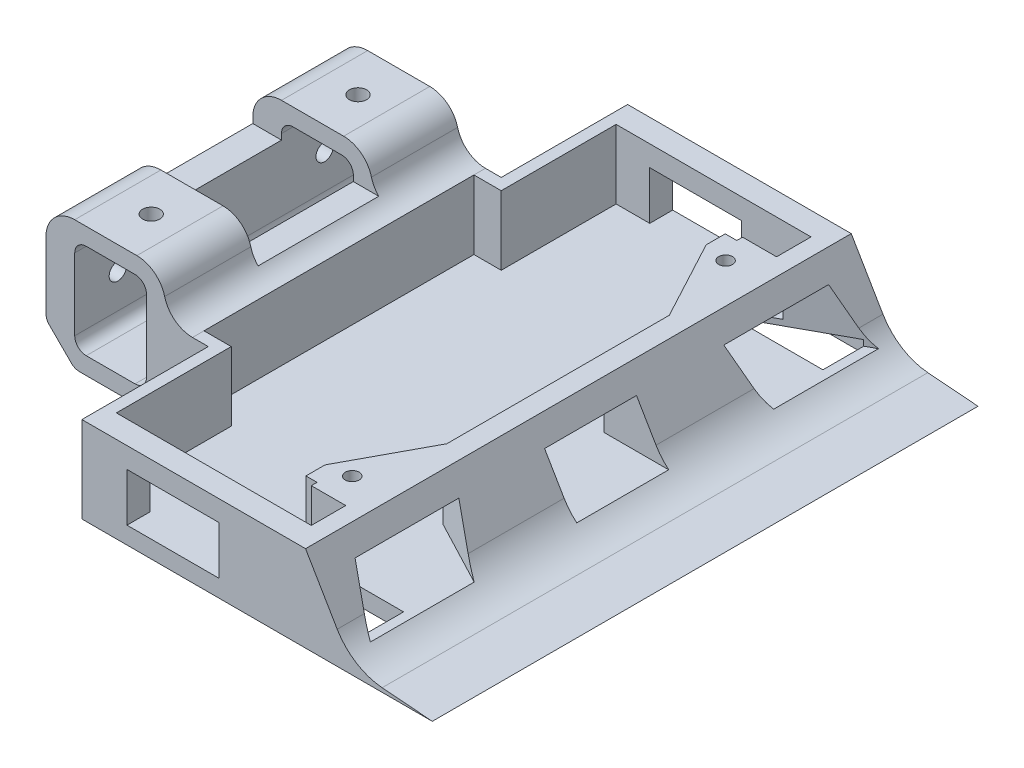
SolidWorks part; units mm, degrees
ref_plane "Front Plane" through (0, 0, 0) normal (0, 0, 1) x (1, 0, 0)
ref_plane "Top Plane" through (0, 0, 0) normal (0, 1, 0) x (1, 0, 0)
ref_plane "Right Plane" through (0, 0, 0) normal (1, 0, 0) x (0, 0, -1)
sketch "Sketch1" plane through (0, 0, 0) normal (0, 1, 0) x (1, 0, 0)
  line L1 (-49.665, 50.1777) -> (45.335, 50.1777)
  line L2 (-49.665, 50.1777) -> (-49.665, -44.8223)
  line L3 (-49.665, -44.8223) -> (45.335, -44.8223)
  line L4 (45.335, 50.1777) -> (45.335, -44.8223)
  dimension "D1" = 95
  dimension "D2" = 95
extrude "Boss-Extrude1" add sketch "Sketch1" along normal blind 20
sketch "Sketch2" plane through (45.335, 0, 0) normal (1, 0, 0) x (0, 0, -1)
  line L0 (-44.8223, 20) -> (-44.8223, 0) construction
  line L1 (-4.8223, 3) -> (10.1777, 3)
  line L2 (-4.8223, 3) -> (-4.8223, 11.4)
  line L3 (-4.8223, 11.4) -> (10.1777, 11.4)
  line L4 (10.1777, 3) -> (10.1777, 11.4)
  line L5 (50.1777, 20) -> (50.1777, 0) construction
  line L6 (-44.8223, 0) -> (50.1777, 0) construction
  dimension "D1" = 15
  dimension "D2" = 8.4
  dimension "D3" = 40
  dimension "D4" = 40
  dimension "D5" = 3
extrude "Cut-Extrude1" cut sketch "Sketch2" against normal blind 50
sketch "Sketch6" plane through (0, 0, 44.8223) normal (0, 0, 1) x (1, 0, 0)
  line L0 (45.335, 0) -> (31.4163, 1.1197)
  line L1 (31.4163, 1.1197) -> (20.335, 20)
  line L2 (-49.665, 20) -> (45.335, 20) construction
  line L3 (20.335, 20) -> (45.335, 20)
  line L4 (45.335, 20) -> (45.335, 0)
  dimension "D1" = 25
extrude "Cut-Extrude3" cut sketch "Sketch6" against normal blind 100
fillet "Fillet1" radius 10 1 edges at (31.4163, 1.1197, -2.6777)
sketch "Sketch7" plane through (0, 20, 0) normal (0, 1, 0) x (1, 0, 0)
  line L0 (11.3607, -29.8223) -> (18.335, -16.5423)
  line L1 (18.335, -16.5423) -> (9.4816, -11.8928)
  line L2 (9.4816, -11.8928) -> (2.5073, -25.1728)
  line L3 (2.5073, -25.1728) -> (11.3607, -29.8223)
  line L4 (20.335, 50.1777) -> (20.335, -44.8223) construction
  line L5 (-49.665, -44.8223) -> (20.335, -44.8223) construction
  line L6 (18.335, 22.0203) -> (11.132, 35.1777)
  line L7 (11.132, 35.1777) -> (2.3604, 30.3757)
  line L8 (2.3604, 30.3757) -> (9.5634, 17.2183)
  line L9 (9.5634, 17.2183) -> (18.335, 22.0203)
  line L10 (20.335, 50.1777) -> (-49.665, 50.1777) construction
  dimension "D1" = 10
  dimension "D2" = 15
  dimension "D3" = 2
  dimension "D4" = 15
  dimension "D5" = 10
  dimension "D6" = 15
  dimension "D7" = 15
  dimension "D8" = 2
extrude "Cut-Extrude4" cut sketch "Sketch7" against normal blind 17
sketch "Sketch8" plane through (12.3274, 0, 6.474) normal (0.8853, 0, 0.465) x (0.465, 0, -0.8853)
  line L0 (-21.1206, 3) -> (-21.1206, 20) construction
  line L1 (-21.1206, 3) -> (-6.1206, 3)
  line L2 (-21.1206, 3) -> (-21.1206, 11.4)
  line L3 (-21.1206, 11.4) -> (-6.1206, 11.4)
  line L4 (-6.1206, 3) -> (-6.1206, 11.4)
  line L5 (-6.1206, 3) -> (-21.1206, 3) construction
  line L6 (-6.1206, 3) -> (-6.1206, 20) construction
  dimension "D1" = 8.4
extrude "Cut-Extrude5" cut sketch "Sketch8" against normal blind 4
sketch "Sketch9" plane through (14.6107, 0, -7.9986) normal (0.8772, 0, -0.4802) x (-0.4802, 0, -0.8772)
  line L0 (25.5109, 3) -> (10.5109, 3) construction
  line L1 (25.5109, 3) -> (10.5109, 3)
  line L2 (25.5109, 3) -> (25.5109, 11.4)
  line L3 (25.5109, 11.4) -> (10.5109, 11.4)
  line L4 (10.5109, 3) -> (10.5109, 11.4)
  line L5 (25.5109, 3) -> (25.5109, 20) construction
  line L6 (10.5109, 3) -> (10.5109, 20) construction
  dimension "D1" = 8.4
extrude "Cut-Extrude6" cut sketch "Sketch9" against normal blind 4
sketch "Sketch10" plane through (8.7861, 0, 4.6142) normal (0.8853, 0, 0.465) x (0.465, 0, -0.8853)
  line L0 (-21.1206, 11.4) -> (-21.1206, 3) construction
  line L1 (-21.1206, 3) -> (-6.1206, 3)
  line L2 (-21.1206, 3) -> (-21.1206, 11.4)
  line L3 (-21.1206, 11.4) -> (-6.1206, 11.4)
  line L4 (-6.1206, 3) -> (-6.1206, 11.4)
  line L5 (-21.1206, 3) -> (-6.1206, 3) construction
  line L6 (-6.1206, 3) -> (-6.1206, 11.4) construction
extrude "Cut-Extrude7" cut sketch "Sketch10" along normal blind 100
sketch "Sketch11" plane through (11.102, 0, -6.0778) normal (0.8772, 0, -0.4802) x (-0.4802, 0, -0.8772)
  line L0 (10.5109, 3) -> (25.5109, 3) construction
  line L1 (25.5109, 3) -> (10.5109, 3)
  line L2 (25.5109, 3) -> (25.5109, 11.4)
  line L3 (25.5109, 11.4) -> (10.5109, 11.4)
  line L4 (10.5109, 3) -> (10.5109, 11.4)
  line L5 (25.5109, 3) -> (25.5109, 11.4) construction
  line L6 (10.5109, 11.4) -> (10.5109, 3) construction
extrude "Cut-Extrude8" cut sketch "Sketch11" along normal blind 100
sketch "Sketch12" plane through (0, 0, 44.8223) normal (0, 0, 1) x (1, 0, 0)
  line L1 (-49.665, 20) -> (46.5626, 20)
  line L2 (-49.665, 20) -> (-49.665, 15)
  line L3 (-49.665, 15) -> (46.5626, 15)
  line L4 (46.5626, 20) -> (46.5626, 15)
  dimension "D1" = 5
extrude "Cut-Extrude9" cut sketch "Sketch12" against normal blind 100
sketch "Sketch14" plane through (11.102, 0, -6.0778) normal (0.8772, 0, -0.4802) x (-0.4802, 0, -0.8772)
  line L0 (10.5109, 11.4) -> (10.5109, 3) construction
  line L1 (10.5109, 3) -> (26.5109, 3)
  line L2 (10.5109, 3) -> (10.5109, 11.4)
  line L3 (10.5109, 11.4) -> (26.5109, 11.4)
  line L4 (26.5109, 3) -> (26.5109, 11.4)
  line L5 (10.5109, 3) -> (25.5109, 3) construction
  line L6 (25.5109, 11.4) -> (10.5109, 11.4) construction
  dimension "D1" = 16
extrude "Cut-Extrude10" cut sketch "Sketch14" along normal blind 100
sketch "Sketch15" plane through (8.7861, 0, 4.6142) normal (0.8853, 0, 0.465) x (0.465, 0, -0.8853)
  line L0 (-6.1206, 3) -> (-6.1206, 11.4) construction
  line L1 (-6.1206, 3) -> (-22.1206, 3)
  line L2 (-6.1206, 3) -> (-6.1206, 11.4)
  line L3 (-6.1206, 11.4) -> (-22.1206, 11.4)
  line L4 (-22.1206, 3) -> (-22.1206, 11.4)
  dimension "D1" = 8.4
  dimension "D2" = 16
extrude "Cut-Extrude11" cut sketch "Sketch15" along normal blind 100
sketch "Sketch16" plane through (-4.665, 0, 0) normal (1, 0, 0) x (0, 0, -1)
  line L0 (-4.8223, 3) -> (-4.8223, 5.6084) construction
  line L1 (-5.3223, 3) -> (10.6777, 3)
  line L2 (-5.3223, 3) -> (-5.3223, 11.4)
  line L3 (-5.3223, 11.4) -> (10.6777, 11.4)
  line L4 (10.6777, 3) -> (10.6777, 11.4)
  line L5 (-5.3223, 3) -> (10.6777, 11.4) construction
  line L6 (-5.3223, 11.4) -> (10.6777, 3) construction
  line L7 (50.1777, 0) -> (-44.8223, 0) construction
  point P0 (2.6777, 7.2)
  point P5 (-4.8223, 4.3042)
  dimension "D1" = 8.4
  dimension "D2" = 16
  dimension "D3" = 0.5
  dimension "D4" = 3
extrude "Cut-Extrude13" cut sketch "Sketch16" along normal blind 100
sketch "Sketch19" plane through (0, 15, 0) normal (0, 1, 0) x (1, 0, 0)
  line L0 (12.1654, -30.8097) -> (19.7472, -16.7201)
  line L1 (12.1851, 36.1278) -> (12.1851, 48.1777)
  line L2 (12.1851, 48.1777) -> (-11.5945, 48.1777)
  line L6 (2.5073, -25.1728) -> (11.3607, -29.8223) construction
  line L7 (12.1851, 36.1278) -> (19.7442, 22.026)
  line L10 (19.7442, 22.026) -> (19.7472, -16.7201)
  line L11 (12.1654, -30.8097) -> (12.1654, -42.8223)
  line L12 (12.1654, -42.8223) -> (-11.5945, -42.8223)
  line L13 (-11.5945, -42.8223) -> (-11.5945, 48.1777)
  line L17 (-49.665, -44.8223) -> (23.2696, -44.8223) construction
  dimension "D4" = 0.5
  dimension "D7" = 2
extrude "Cut-Extrude16" cut sketch "Sketch19" against normal blind 12
sketch "Sketch21" plane through (0, 3, 0) normal (0, 1, 0) x (1, 0, 0)
  line L0 (-11.5945, 48.1777) -> (-11.5945, -42.8223) construction
  line L1 (12.1851, 48.1777) -> (-11.5945, 48.1777)
  line L2 (12.1851, 48.1777) -> (12.1851, 46.1777)
  line L3 (12.1851, 46.1777) -> (-11.5945, 46.1777)
  line L4 (-11.5945, 48.1777) -> (-11.5945, 46.1777)
  dimension "D1" = 2
extrude "Boss-Extrude2" add sketch "Sketch21" along normal blind 12
sketch "Sketch23" plane through (0, 3, 0) normal (0, 1, 0) x (1, 0, 0)
  line L0 (-11.5945, 46.1777) -> (-11.5945, -42.8223) construction
  line L1 (12.1654, -42.8223) -> (-11.5945, -42.8223)
  line L2 (12.1654, -42.8223) -> (12.1654, -40.8223)
  line L3 (12.1654, -40.8223) -> (-11.5945, -40.8223)
  line L4 (-11.5945, -42.8223) -> (-11.5945, -40.8223)
  dimension "D1" = 2
extrude "Boss-Extrude3" add sketch "Sketch23" along normal blind 12
sketch "Sketch24" plane through (0, 0, -46.1777) normal (0, 0, 1) x (1, 0, 0)
  line L0 (-11.5945, 3) -> (12.1851, 3) construction
  line L1 (-7.8145, 3) -> (7.1855, 3)
  line L2 (-7.8145, 3) -> (-7.8145, 11.4)
  line L3 (-7.8145, 11.4) -> (7.1855, 11.4)
  line L4 (7.1855, 3) -> (7.1855, 11.4)
  line L5 (-11.5945, 15) -> (-11.5945, 3) construction
  dimension "D1" = 15
  dimension "D2" = 8.4
  dimension "D3" = 3.78
  dimension "D4" = 4.9995
extrude "Cut-Extrude19" cut sketch "Sketch24" against normal blind 100 and the other way blind 100
sketch "Sketch26" plane through (0, 15, 0) normal (0, 1, 0) x (1, 0, 0)
  line L0 (-49.665, 50.1777) -> (23.2696, 50.1777) construction
  line L1 (-49.665, -44.8223) -> (-29.665, -44.8223)
  line L2 (-49.665, -44.8223) -> (-49.665, 50.1777)
  line L3 (-49.665, 50.1777) -> (-29.665, 50.1777)
  line L4 (-29.665, -44.8223) -> (-29.665, 50.1777)
  dimension "D1" = 20
extrude "Boss-Extrude4" add sketch "Sketch26" along normal blind 20
sketch "Sketch31" plane through (-29.665, 0, 0) normal (1, 0, 0) x (0, 0, -1)
  line L1 (-44.8223, 35) -> (50.1777, 35)
  line L2 (-44.8223, 35) -> (-44.8223, 15)
  line L3 (-44.8223, 15) -> (50.1777, 15)
  line L4 (50.1777, 35) -> (50.1777, 15)
extrude "Boss-Extrude6" add sketch "Sketch31" along normal blind 10
sketch "Sketch32" plane through (0, 0, -50.1777) normal (0, 0, -1) x (-1, 0, 0)
  line L0 (49.665, 35) -> (49.665, 0) construction
  line L1 (38.915, 19.5) -> (26.415, 19.5)
  line L2 (38.915, 19.5) -> (38.915, 3)
  line L3 (38.915, 3) -> (26.415, 3)
  line L4 (26.415, 19.5) -> (26.415, 3)
  line L5 (-45.335, 0) -> (49.665, 0) construction
  dimension "D1" = 12.5
  dimension "D2" = 16.5
  dimension "D3" = 10.75
  dimension "D4" = 3
extrude "Cut-Extrude22" cut sketch "Sketch32" against normal blind 100
sketch "Sketch33" plane through (0, 0, -50.1777) normal (0, 0, -1) x (-1, 0, 0)
  line L0 (19.665, 35) -> (49.665, 35) construction
  line L1 (19.665, 15) -> (23.415, 15)
  line L2 (19.665, 15) -> (19.665, 35)
  line L3 (19.665, 35) -> (23.415, 35)
  line L4 (23.415, 15) -> (23.415, 35)
  line L5 (26.415, 19.5) -> (26.415, 3) construction
  dimension "D1" = 3
extrude "Cut-Extrude23" cut sketch "Sketch33" against normal blind 100
sketch "Sketch34" plane through (0, 0, -50.1777) normal (0, 0, -1) x (-1, 0, 0)
  line L0 (49.665, 35) -> (49.665, 0) construction
  line L1 (23.415, 35) -> (49.665, 35)
  line L2 (23.415, 35) -> (23.415, 22.5)
  line L3 (23.415, 22.5) -> (49.665, 22.5)
  line L4 (49.665, 35) -> (49.665, 22.5)
  dimension "D1" = 3
extrude "Cut-Extrude24" cut sketch "Sketch34" against normal blind 100
sketch "Sketch35" plane through (0, 0, -50.1777) normal (0, 0, -1) x (-1, 0, 0)
  line L1 (49.665, 0) -> (15.665, 0)
  line L2 (49.665, 0) -> (49.665, 47.0729)
  line L3 (49.665, 47.0729) -> (15.665, 47.0729)
  line L4 (15.665, 0) -> (15.665, 47.0729)
  dimension "D1" = 34
extrude "Cut-Extrude25" cut sketch "Sketch35" against normal blind 22
sketch "Sketch36" plane through (0, 0, 44.8223) normal (0, 0, 1) x (1, 0, 0)
  line L1 (-49.665, 0) -> (-15.665, 0)
  line L2 (-49.665, 0) -> (-49.665, 30.6044)
  line L3 (-49.665, 30.6044) -> (-15.665, 30.6044)
  line L4 (-15.665, 0) -> (-15.665, 30.6044)
  dimension "D1" = 34
extrude "Cut-Extrude26" cut sketch "Sketch36" against normal blind 22
sketch "Sketch37" plane through (0, 22.5, 0) normal (0, 1, 0) x (1, 0, 0)
  line L0 (-49.665, -22.8223) -> (-49.665, 28.1777) construction
  line L1 (-49.665, 13.1777) -> (-23.415, 13.1777)
  line L2 (-49.665, 13.1777) -> (-49.665, -7.8223)
  line L3 (-49.665, -7.8223) -> (-23.415, -7.8223)
  line L4 (-23.415, 13.1777) -> (-23.415, -7.8223)
  line L5 (-23.415, 28.1777) -> (-23.415, -22.8223) construction
  dimension "D1" = 15
  dimension "D2" = 15
extrude "Cut-Extrude28" cut sketch "Sketch37" against normal blind 6
sketch "Sketch38" plane through (0, 0, 22.8223) normal (0, 0, 1) x (1, 0, 0)
  line L0 (-49.665, 0) -> (-15.665, 0) construction
  line L1 (-49.665, 22.5) -> (-43.915, 22.5)
  line L2 (-49.665, 22.5) -> (-49.665, 0)
  line L3 (-49.665, 0) -> (-43.915, 0)
  line L4 (-43.915, 22.5) -> (-43.915, 0)
  line L5 (-38.915, 19.5) -> (-38.915, 3) construction
  dimension "D1" = 5
extrude "Cut-Extrude29" cut sketch "Sketch38" against normal blind 100
chamfer "Chamfer1" distance 5 angle 45 1 edges at (-43.915, 0, -2.6777)
sketch "Sketch39" plane through (0, 15, 0) normal (0, 1, 0) x (1, 0, 0)
  line L0 (-15.665, -22.8223) -> (-15.665, -44.8223) construction
  line L1 (-11.5945, 46.1777) -> (-13.665, 46.1777)
  line L2 (-11.5945, 46.1777) -> (-11.5945, -40.8223)
  line L3 (-11.5945, -40.8223) -> (-13.665, -40.8223)
  line L4 (-13.665, 46.1777) -> (-13.665, -40.8223)
  line L5 (-15.665, -44.8223) -> (23.2696, -44.8223) construction
  dimension "D1" = 2
  dimension "D2" = 4
extrude "Cut-Extrude30" cut sketch "Sketch39" against normal blind 12
fillet "Fillet4" radius 5 1 edges at (-23.415, 15, -2.6777)
fillet "Fillet5" radius 5 2 edges at (-23.415, 22.5, 15.3223) (-23.415, 22.5, -20.6777)
sketch "Sketch40" plane through (0, 15, 0) normal (0, 1, 0) x (1, 0, 0)
  line L0 (-13.665, 46.1777) -> (-13.665, -40.8223) construction
  line L1 (-13.665, -20.8223) -> (-18.415, -20.8223)
  line L2 (-13.665, -20.8223) -> (-13.665, 26.1777)
  line L3 (-13.665, 26.1777) -> (-18.415, 26.1777)
  line L4 (-18.415, -20.8223) -> (-18.415, 26.1777)
  line L5 (-18.415, 28.1777) -> (-18.415, -22.8223) construction
  dimension "D1" = 2
  dimension "D2" = 2
extrude "Cut-Extrude31" cut sketch "Sketch40" against normal blind 12
fillet "Fillet6" radius 5 2 edges at (-43.915, 22.5, -20.6777) (-43.915, 22.5, 15.3223)
sketch "Sketch46" plane through (0, 0, 0) normal (0, -1, 0) x (-1, 0, 0)
  line L0 (15.665, -44.8223) -> (-45.335, -44.8223) construction
  line L1 (-29.335, -42.8223) -> (-12.335, -42.8223)
  line L2 (-29.335, -42.8223) -> (-29.335, -33.8223)
  line L3 (-29.335, -33.8223) -> (-12.335, -33.8223)
  line L4 (-12.335, -42.8223) -> (-12.335, -33.8223)
  line L5 (-45.335, -44.8223) -> (-45.335, 50.1777) construction
  line L6 (-45.335, 50.1777) -> (15.665, 50.1777) construction
  line L7 (-12.335, 39.1777) -> (-29.335, 39.1777)
  line L8 (-12.335, 39.1777) -> (-12.335, 48.1777)
  line L9 (-12.335, 48.1777) -> (-29.335, 48.1777)
  line L10 (-29.335, 39.1777) -> (-29.335, 48.1777)
  point P4 (-14.835, -44.8223)
  dimension "D1" = 9
  dimension "D2" = 17
  dimension "D3" = 2
  dimension "D4" = 16
  dimension "D5" = 9
  dimension "D6" = 17
  dimension "D7" = 2
  dimension "D8" = 16
extrude "Cut-Extrude36" cut sketch "Sketch46" against normal blind 4
sketch "Sketch47" plane through (0, 4, 0) normal (0, -1, 0) x (-1, 0, 0)
  line L0 (-12.335, -42.8223) -> (-12.335, -33.8223) construction
  line L2 (-12.335, -33.8223) -> (-29.335, -33.8223) construction
  line L3 (-29.335, -42.8223) -> (-12.335, -42.8223) construction
  line L4 (-12.335, 48.1777) -> (-29.335, 48.1777) construction
  line L5 (-12.335, 39.1777) -> (-12.335, 48.1777) construction
  circle A0 centre (-17.335, -38.3223) radius 1.25
  circle A1 centre (-17.335, 43.6777) radius 1.25
  point P2 (-12.335, -38.3223)
  point P15 (-10.8829, 45.8069)
  dimension "D1" = 5
  dimension "D4" = 2.5
  dimension "D5" = 2.5
  dimension "D2" = 4.5
  dimension "D3" = 4.5
  dimension "D6" = 4.5
  dimension "D7" = 5
extrude "Cut-Extrude37" cut sketch "Sketch47" against normal blind 100
sketch "Sketch48" plane through (0, 15, 0) normal (0, 1, 0) x (1, 0, 0)
  line L0 (23.2696, 50.1777) -> (23.2696, -44.8223) construction
  line L1 (14.2696, -40.8223) -> (20.2696, -40.8223)
  line L2 (14.2696, -40.8223) -> (14.2696, -34.8223)
  line L3 (14.2696, -34.8223) -> (20.2696, -34.8223)
  line L4 (20.2696, -40.8223) -> (20.2696, -34.8223)
  line L5 (-15.665, -44.8223) -> (23.2696, -44.8223) construction
  line L6 (-15.665, 50.1777) -> (23.2696, 50.1777) construction
  line L7 (14.2696, 40.1777) -> (20.2696, 40.1777)
  line L8 (14.2696, 40.1777) -> (14.2696, 46.1777)
  line L9 (14.2696, 46.1777) -> (20.2696, 46.1777)
  line L10 (20.2696, 40.1777) -> (20.2696, 46.1777)
  dimension "D1" = 6
  dimension "D2" = 6
  dimension "D3" = 3
  dimension "D4" = 4
  dimension "D5" = 6
  dimension "D6" = 4
  dimension "D7" = 3
  dimension "D8" = 0
extrude "Cut-Extrude40" cut sketch "Sketch48" against normal blind 10
sketch "Sketch49" plane through (0, 15, 0) normal (0, 1, 0) x (1, 0, 0)
  line L1 (12.1654, -40.8223) -> (14.2696, -40.8223)
  line L2 (12.1654, -40.8223) -> (12.1654, -34.8223)
  line L3 (12.1654, -34.8223) -> (14.2696, -34.8223)
  line L4 (14.2696, -40.8223) -> (14.2696, -34.8223)
  line L5 (14.2696, 40.1777) -> (12.1851, 40.1777)
  line L6 (14.2696, 40.1777) -> (14.2696, 46.1777)
  line L7 (14.2696, 46.1777) -> (12.1851, 46.1777)
  line L8 (12.1851, 40.1777) -> (12.1851, 46.1777)
extrude "Cut-Extrude41" cut sketch "Sketch49" against normal blind 20
sketch "Sketch50" plane through (0, 0, 0) normal (0, -1, 0) x (-1, 0, 0)
  line L1 (-12.335, -42.8223) -> (-9.335, -42.8223)
  line L2 (-12.335, -42.8223) -> (-12.335, -33.8223)
  line L3 (-12.335, -33.8223) -> (-9.335, -33.8223)
  line L4 (-9.335, -42.8223) -> (-9.335, -33.8223)
  line L5 (-12.335, 39.1777) -> (-9.335, 39.1777)
  line L6 (-12.335, 39.1777) -> (-12.335, 48.1777)
  line L7 (-12.335, 48.1777) -> (-9.335, 48.1777)
  line L8 (-9.335, 39.1777) -> (-9.335, 48.1777)
  dimension "D1" = 9
  dimension "D2" = 3
  dimension "D3" = 9
extrude "Cut-Extrude42" cut sketch "Sketch50" against normal blind 20
sketch "Sketch51" plane through (0, 0, 42.8223) normal (0, 0, -1) x (-1, 0, 0)
  line L0 (-29.335, 0) -> (-9.335, 0) construction
  line L1 (-9.335, 15) -> (-12.335, 15)
  line L2 (-9.335, 15) -> (-9.335, 0)
  line L3 (-9.335, 0) -> (-12.335, 0)
  line L4 (-12.335, 15) -> (-12.335, 0)
  dimension "D1" = 3
extrude "Boss-Extrude7" add sketch "Sketch51" along normal blind 2
sketch "Sketch52" plane through (0, 0, -48.1777) normal (0, 0, 1) x (1, 0, 0)
  line L0 (9.335, 0) -> (29.335, 0) construction
  line L1 (9.335, 15) -> (12.335, 15)
  line L2 (9.335, 15) -> (9.335, 0)
  line L3 (9.335, 0) -> (12.335, 0)
  line L4 (12.335, 15) -> (12.335, 0)
  dimension "D1" = 3
extrude "Boss-Extrude8" add sketch "Sketch52" along normal blind 2
sketch "Sketch53" plane through (0, 15, 0) normal (0, 1, 0) x (1, 0, 0)
  line L1 (12.335, -34.8223) -> (0, -34.8223)
  line L2 (12.335, -34.8223) -> (12.335, 41.2402)
  line L3 (12.335, 41.2402) -> (0, 41.2402)
  line L4 (0, -34.8223) -> (0, 41.2402)
extrude "Cut-Extrude43" cut sketch "Sketch53" against normal blind 12
sketch "Sketch54" plane through (0, 4, 0) normal (0, -1, 0) x (-1, 0, 0)
  line L1 (-14.2696, -34.8223) -> (-12.335, -34.8223)
  line L2 (-14.2696, -34.8223) -> (-14.2696, -33.8223)
  line L3 (-14.2696, -33.8223) -> (-12.335, -33.8223)
  line L4 (-12.335, -34.8223) -> (-12.335, -33.8223)
extrude "Cut-Extrude44" cut sketch "Sketch54" against normal blind 20
sketch "Sketch55" plane through (0, 4, 0) normal (0, -1, 0) x (-1, 0, 0)
  line L0 (-16.3562, 39.1777) -> (-12.335, 39.1777) construction
  line L1 (-12.335, 40.1777) -> (-14.3456, 40.1777)
  line L2 (-12.335, 40.1777) -> (-12.335, 39.1777)
  line L3 (-12.335, 39.1777) -> (-14.3456, 39.1777)
  line L4 (-14.3456, 40.1777) -> (-14.3456, 39.1777)
extrude "Cut-Extrude45" cut sketch "Sketch55" against normal blind 20
sketch "Sketch56" plane through (0, 22.5, 0) normal (0, 1, 0) x (1, 0, 0)
  line L0 (-38.915, 28.1777) -> (-28.0975, 28.1777) construction
  line L1 (-38.915, -22.8223) -> (-28.0975, -22.8223) construction
  line L2 (-38.915, -7.8223) -> (-28.0975, -7.8223) construction
  line L3 (-28.0975, -22.8223) -> (-28.0975, -7.8223) construction
  line L4 (-38.915, -7.8223) -> (-38.915, -22.8223) construction
  line L5 (-28.0975, 13.1777) -> (-28.0975, 28.1777) construction
  circle A0 centre (-33.0975, -15.3223) radius 1.5
  circle A1 centre (-33.0975, 20.6777) radius 1.5
  point P4 (-33.5063, 28.1777)
  point P9 (-33.5063, -7.8223)
  point P12 (-28.0975, -15.3223)
  point P15 (-38.915, -15.3223)
  point P18 (-28.0975, 20.6777)
  dimension "D1" = 7.5
  dimension "D2" = 7.5
  dimension "D3" = 7.5
  dimension "D4" = 5
  dimension "D5" = 5.8175
  dimension "D6" = 5
extrude "Cut-Extrude46" cut sketch "Sketch56" against normal blind 10
sketch "Sketch57" plane through (-43.915, 0, 0) normal (-1, 0, 0) x (0, 0, 1)
  line L0 (22.8223, 5) -> (22.8223, 17.5) construction
  line L1 (-28.1777, 17.5) -> (-28.1777, 5) construction
  line L2 (-28.1777, 5) -> (22.8223, 5) construction
  circle A0 centre (-20.6777, 11) radius 1.5
  circle A1 centre (15.3223, 11) radius 1.5
  point P6 (-28.1777, 11.25)
  dimension "D1" = 7.5
  dimension "D2" = 7.5
  dimension "D3" = 6
  dimension "D4" = 6
extrude "Cut-Extrude47" cut sketch "Sketch57" against normal blind 10
fillet "Fillet11" radius 2 2 edges at (-43.915, 5, -2.6777) (-38.915, 0, -2.6777)
sketch "Sketch58" plane through (0, 15, 0) normal (0, 1, 0) x (1, 0, 0)
  line L0 (14.3456, 40.1777) -> (20.2696, 40.1777) construction
  line L1 (20.2696, -34.8223) -> (14.2696, -34.8223) construction
  circle A0 centre (16.395, 35.1777) radius 1.2
  circle A1 centre (16.395, -29.8223) radius 1.2
  point P6 (17.2696, -34.8223)
  dimension "D1" = 65
  dimension "D2" = 5
  dimension "D3" = 5
extrude "Cut-Extrude48" cut sketch "Sketch58" against normal blind 10
sketch "Sketch59" plane through (0, 0, 44.8223) normal (0, 0, 1) x (1, 0, 0)
  line L1 (-7.8145, 11.4) -> (8.1855, 11.4)
  line L2 (-7.8145, 11.4) -> (-7.8145, 3)
  line L3 (-7.8145, 3) -> (8.1855, 3)
  line L4 (8.1855, 11.4) -> (8.1855, 3)
  dimension "D1" = 16
extrude "Cut-Extrude49" cut sketch "Sketch59" against normal blind 9090
fillet "Fillet14" radius 2 2 edges at (-26.415, 3, -2.6777) (-38.915, 3, -2.6777)
fillet "Fillet15" radius 2 1 edges at (-38.915, 19.5, 15.3223)
fillet "Fillet16" radius 2 1 edges at (-38.915, 19.5, -20.6777)
fillet "Fillet17" radius 2 1 edges at (-26.415, 19.5, 15.3223)
fillet "Fillet18" radius 2 1 edges at (-26.415, 19.5, -20.6777)
